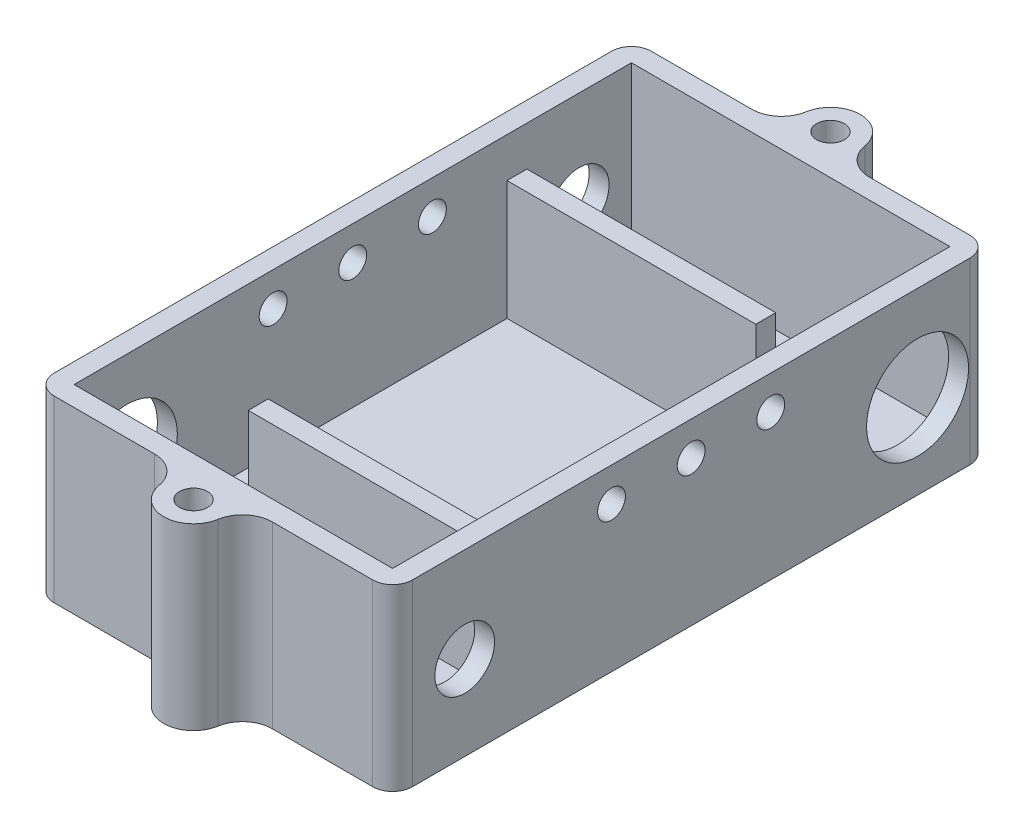
SolidWorks part; units mm, degrees
ref_plane "前视基准面" through (0, 0, 0) normal (0, 0, 1) x (1, 0, 0)
ref_plane "上视基准面" through (0, 0, 0) normal (0, 1, 0) x (1, 0, 0)
ref_plane "右视基准面" through (0, 0, 0) normal (1, 0, 0) x (0, 0, -1)
sketch "草图1" plane through (0, 0, 0) normal (0, 1, 0) x (1, 0, 0)
  line L1 (-18, 30) -> (18, 30)
  line L2 (-18, 30) -> (-18, -30)
  line L3 (-18, -30) -> (18, -30)
  line L4 (18, 30) -> (18, -30)
  dimension "D1" = 36
  dimension "D2" = 60
  dimension "D3" = 30
  dimension "D4" = 18
extrude "凸台-拉伸1" add sketch "草图1" along normal blind 18
fillet "圆角1" radius 2 4 edges at (-18, 9, -30) (18, 9, -30) (18, 9, 30) (-18, 9, 30)
shell "抽壳1" thickness 2 removed face at (0, 18, 0)
sketch "草图2" plane through (0, 2, 0) normal (0, 1, 0) x (1, 0, 0)
  line L0 (16, -28) -> (16, 28) construction
  line L1 (16, -17.5) -> (-9, -17.5)
  line L2 (16, -17.5) -> (16, -15.5)
  line L3 (16, -15.5) -> (-9, -15.5)
  line L4 (-9, -17.5) -> (-9, -15.5)
  dimension "D1" = 25
  dimension "D2" = 0
  dimension "D3" = 12.5
  dimension "D4" = 2
extrude "凸台-拉伸2" add sketch "草图2" along normal blind 12
sketch "草图3" plane through (18, 0, 0) normal (1, 0, 0) x (0, 0, -1)
  line L0 (-28, 0) -> (28, 0) construction
  line L1 (-30, 0) -> (-30, 18) construction
  circle A0 centre (-22.75, 8.5) radius 3
  dimension "D1" = 8.5
  dimension "D3" = 6
  dimension "D2" = 7.25
extrude "切除-拉伸1" cut sketch "草图3" against normal blind 14
sketch "草图4" plane through (0, 18, 0) normal (0, 1, 0) x (1, 0, 0)
  line L0 (16, 30) -> (-16, 30) construction
  line L1 (-29.2902, 0) -> (20.3844, 0) construction
  circle A0 centre (0, 32) radius 3
  circle A1 centre (0, -32) radius 3
  dimension "D1" = 6
  dimension "D2" = 2
extrude "凸台-拉伸3" add sketch "草图4" against normal blind 18
fillet "圆角2" radius 3 4 edges at (-2.2361, 9, 30) (2.2361, 9, 30) (-2.2361, 9, -30) (2.2361, 9, -30)
sketch "草图6" plane through (0, 2, 0) normal (0, 1, 0) x (1, 0, 0)
  line L0 (-16, 28) -> (-16, -28) construction
  line L1 (-16, 17.5) -> (9, 17.5)
  line L2 (-16, 17.5) -> (-16, 15.5)
  line L3 (-16, 15.5) -> (9, 15.5)
  line L4 (9, 17.5) -> (9, 15.5)
  line L5 (16, 28) -> (-16, 28) construction
  dimension "D1" = 2
  dimension "D2" = 10.5
  dimension "D3" = 25
extrude "凸台-拉伸4" add sketch "草图6" along normal blind 12
sketch "草图8" plane through (-18, 0, 0) normal (-1, 0, 0) x (0, 0, 1)
  line L0 (-30, 18) -> (-30, 0) construction
  line L1 (-28, 0) -> (28, 0) construction
  circle A0 centre (-22.75, 8.5) radius 3
  dimension "D1" = 7.25
  dimension "D2" = 8.5
extrude "切除-拉伸2" cut sketch "草图8" against normal blind 14
sketch "草图9" plane through (0, 18, 0) normal (0, 1, 0) x (1, 0, 0)
  circle A0 centre (0, 32) radius 1.4
  circle A1 centre (0, -32) radius 1.4
extrude "切除-拉伸3" cut sketch "草图9" against normal blind 10
sketch "草图11" plane through (18, 0, 0) normal (1, 0, 0) x (0, 0, -1)
  line L0 (-28, 18) -> (28, 18) construction
  circle A0 centre (-8, 14.6) radius 1.4
  circle A1 centre (0, 14.6) radius 1.4
  circle A2 centre (8, 14.6) radius 1.4
  dimension "D1" = 3.4
  dimension "D2" = 2.8
  dimension "D3" = 2.8
  dimension "D4" = 8
  dimension "D5" = 0
  dimension "D6" = 8
extrude "切除-拉伸5" cut sketch "草图11" against normal blind 66
sketch "草图13" plane through (16, 0, 0) normal (-1, 0, 0) x (0, 0, 1)
  line L0 (0, 30.997) -> (0, -7.3331) construction
  circle A0 centre (-22.75, 8.5) radius 5.125
extrude "切除-拉伸6" cut sketch "草图13" against normal blind 66
sketch "草图14" plane through (-16, 0, 0) normal (1, 0, 0) x (0, 0, -1)
  circle A0 centre (-22.75, 8.5) radius 5.125
extrude "切除-拉伸7" cut sketch "草图14" against normal blind 66
